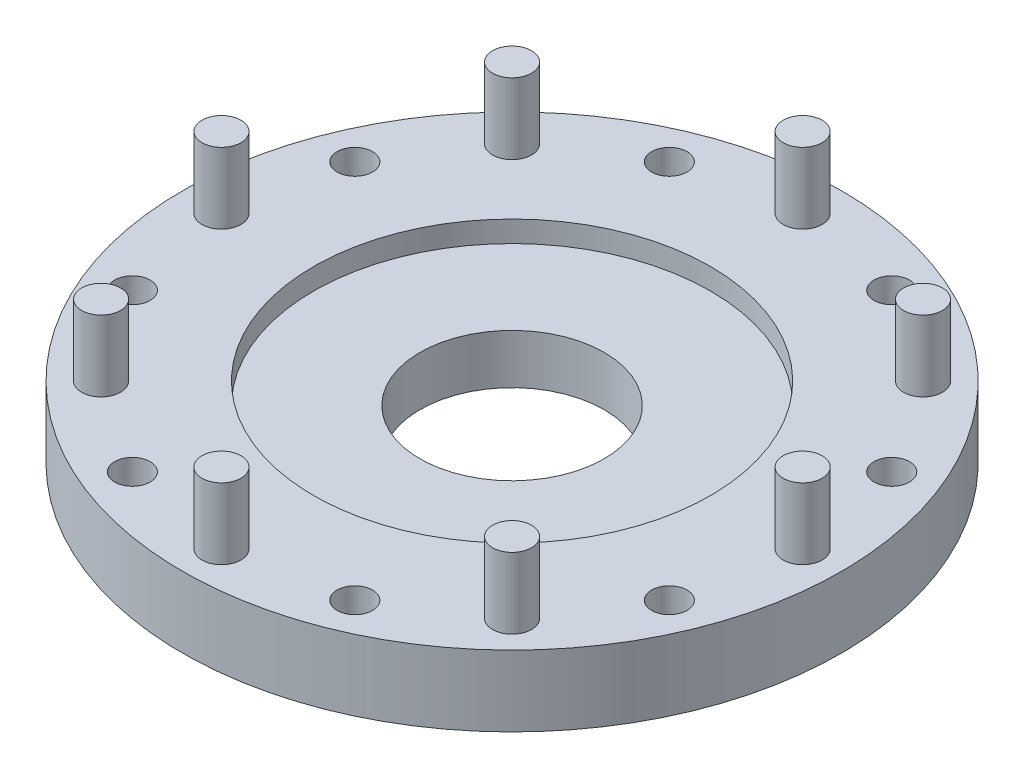
SolidWorks part; units mm, degrees
material "ABS"
ref_plane "Front Plane" through (0, 0, 0) normal (0, 0, 1) x (1, 0, 0)
ref_plane "Top Plane" through (0, 0, 0) normal (0, 1, 0) x (1, 0, 0)
ref_plane "Right Plane" through (0, 0, 0) normal (1, 0, 0) x (0, 0, -1)
sketch "Sketch1" plane through (0, 0, 0) normal (0, 0, 1) x (1, 0, 0)
  line L0 (0, -1.7519) -> (0, 48.3018) construction
  line L1 (-28, 10) -> (-46.5, 10)
  line L4 (-46.5, 10) -> (-46.5, 0)
  line L5 (-46.5, 0) -> (-13, 0)
  line L6 (-13, 0) -> (-13, 7)
  line L7 (-13, 7) -> (-28, 7)
  line L8 (-28, 7) -> (-28, 10)
  point P5 (0, 0)
  point P6 (0, 0)
  point P11 (0, 0)
  point P12 (-10.5, 31.1539)
  point P13 (-28, 36.7952)
  point P14 (0, 0)
  dimension "D1" = 46.5
  dimension "D3" = 3
  dimension "D2" = 28
  dimension "D4" = 13
  dimension "D5" = 10
revolve "Revolve1" add sketch "Sketch1" angle 360 about L0
sketch "Sketch2" plane through (0, 10, 0) normal (0, 1, 0) x (1, 0, 0)
  line L0 (0, 41) -> (0, 0) construction
  line L1 (0, 0) -> (15.69, 37.8791) construction
  circle A0 centre (0, 0) radius 41 construction
  circle A1 centre (0, 41) radius 2.75
  circle A2 centre (15.69, 37.8791) radius 2.5
  circle A3 centre (28.9914, 28.9914) radius 2.75
  circle A4 centre (37.8791, 15.69) radius 2.5
  circle A5 centre (41, 0) radius 2.75
  circle A6 centre (37.8791, -15.69) radius 2.5
  circle A7 centre (28.9914, -28.9914) radius 2.75
  circle A8 centre (15.69, -37.8791) radius 2.5
  circle A9 centre (0, -41) radius 2.75
  circle A10 centre (-15.69, -37.8791) radius 2.5
  circle A11 centre (-28.9914, -28.9914) radius 2.75
  circle A12 centre (-37.8791, -15.69) radius 2.5
  circle A13 centre (-41, 0) radius 2.75
  circle A14 centre (-37.8791, 15.69) radius 2.5
  circle A15 centre (-28.9914, 28.9914) radius 2.75
  circle A16 centre (-15.69, 37.8791) radius 2.5
  point P8 (0, 0)
  point P9 (0, 0)
  point P37 (0, 0)
  dimension "D1" = 82
  dimension "D2" = 5.5
  dimension "D3" = 5
  dimension "D4" = 22.5
  dimension "D5" = 8
extrude "Cut-Extrude1" cut sketch "Sketch2" against normal through all both and the other way through all
sketch "Sketch3" plane through (0, 0, 0) normal (0, 0, 1) x (1, 0, 0)
  line L0 (27.5, 4) -> (27.5, 0)
  line L2 (27.5, 0) -> (22.5, 0)
  line L3 (22.5, 0) -> (22.5, 4)
  line L6 (25, 4) -> (25, 0) construction
  line L7 (0, -19.0654) -> (0, 22.7714) construction
  line L8 (-46.5, 0) -> (46.5, 0) construction
  line L9 (27.5, 4) -> (22.5, 4)
  point P2 (25, 3.3621)
  dimension "D1" = 25
  dimension "D2" = 4
  dimension "D3" = 5
revolve "Cut-Revolve1" cut sketch "Sketch3" angle 360 about L7
sketch "Sketch4" plane through (0, 0, 0) normal (0, -1, 0) x (1, 0, 0)
  line L0 (-19.1541, 39.8791) -> (-19.1541, 35.8791)
  line L1 (-19.1541, 35.8791) -> (-15.69, 33.8791)
  line L2 (-15.69, 33.8791) -> (-12.2259, 35.8791)
  line L3 (-12.2259, 35.8791) -> (-12.2259, 39.8791)
  line L4 (-12.2259, 39.8791) -> (-15.69, 41.8791)
  line L5 (-15.69, 41.8791) -> (-19.1541, 39.8791)
  line L6 (-15.69, 41.8791) -> (-15.69, 33.8791) construction
  line L7 (18.5184, 40.7075) -> (14.6547, 41.7428)
  line L8 (14.6547, 41.7428) -> (11.8263, 38.9143)
  line L9 (11.8263, 38.9143) -> (12.8616, 35.0506)
  line L10 (12.8616, 35.0506) -> (16.7253, 34.0154)
  line L11 (16.7253, 34.0154) -> (19.5537, 36.8438)
  line L12 (19.5537, 36.8438) -> (18.5184, 40.7075)
  line L13 (41.8791, 15.69) -> (39.8791, 19.1541)
  line L14 (39.8791, 19.1541) -> (35.8791, 19.1541)
  line L15 (35.8791, 19.1541) -> (33.8791, 15.69)
  line L16 (33.8791, 15.69) -> (35.8791, 12.2259)
  line L17 (35.8791, 12.2259) -> (39.8791, 12.2259)
  line L18 (39.8791, 12.2259) -> (41.8791, 15.69)
  line L19 (40.7075, -18.5184) -> (41.7428, -14.6547)
  line L20 (41.7428, -14.6547) -> (38.9143, -11.8263)
  line L21 (38.9143, -11.8263) -> (35.0506, -12.8616)
  line L22 (35.0506, -12.8616) -> (34.0154, -16.7253)
  line L23 (34.0154, -16.7253) -> (36.8438, -19.5537)
  line L24 (36.8438, -19.5537) -> (40.7075, -18.5184)
  line L25 (15.69, -41.8791) -> (19.1541, -39.8791)
  line L26 (19.1541, -39.8791) -> (19.1541, -35.8791)
  line L27 (19.1541, -35.8791) -> (15.69, -33.8791)
  line L28 (15.69, -33.8791) -> (12.2259, -35.8791)
  line L29 (12.2259, -35.8791) -> (12.2259, -39.8791)
  line L30 (12.2259, -39.8791) -> (15.69, -41.8791)
  line L31 (-18.5184, -40.7075) -> (-14.6547, -41.7428)
  line L32 (-14.6547, -41.7428) -> (-11.8263, -38.9143)
  line L33 (-11.8263, -38.9143) -> (-12.8616, -35.0506)
  line L34 (-12.8616, -35.0506) -> (-16.7253, -34.0154)
  line L35 (-16.7253, -34.0154) -> (-19.5537, -36.8438)
  line L36 (-19.5537, -36.8438) -> (-18.5184, -40.7075)
  line L37 (-41.8791, -15.69) -> (-39.8791, -19.1541)
  line L38 (-39.8791, -19.1541) -> (-35.8791, -19.1541)
  line L39 (-35.8791, -19.1541) -> (-33.8791, -15.69)
  line L40 (-33.8791, -15.69) -> (-35.8791, -12.2259)
  line L41 (-35.8791, -12.2259) -> (-39.8791, -12.2259)
  line L42 (-39.8791, -12.2259) -> (-41.8791, -15.69)
  line L43 (-40.7075, 18.5184) -> (-41.7428, 14.6547)
  line L44 (-41.7428, 14.6547) -> (-38.9143, 11.8263)
  line L45 (-38.9143, 11.8263) -> (-35.0506, 12.8616)
  line L46 (-35.0506, 12.8616) -> (-34.0154, 16.7253)
  line L47 (-34.0154, 16.7253) -> (-36.8438, 19.5537)
  line L48 (-36.8438, 19.5537) -> (-40.7075, 18.5184)
  line L49 (11.8263, 38.9143) -> (19.5537, 36.8438) construction
  circle A0 centre (15.69, 37.8791) radius 2.5 construction
  circle A1 centre (0, 41) radius 2.75 construction
  circle A2 centre (0, 41) radius 2.75 construction
  circle A3 centre (15.69, 37.8791) radius 2.5 construction
  circle A4 centre (-15.69, 37.8791) radius 2.5 construction
  circle A5 centre (-15.69, 37.8791) radius 2.5 construction
  point P57 (0, 0)
  point P58 (0, 0)
  dimension "D1" = 120
  dimension "D2" = 120
  dimension "D3" = 8
  dimension "D4" = 8
extrude "Cut-Extrude2" cut sketch "Sketch4" against normal blind 5
sketch "Sketch5" plane through (0, 0, 0) normal (0, -1, 0) x (1, 0, 0)
  circle A0 centre (0, 41) radius 2.75 construction
  circle A1 centre (0, 41) radius 2.75
  circle A2 centre (28.9914, 28.9914) radius 2.75 construction
  circle A3 centre (41, 0) radius 2.75 construction
  circle A4 centre (28.9914, -28.9914) radius 2.75 construction
  circle A5 centre (0, -41) radius 2.75 construction
  circle A6 centre (-28.9914, -28.9914) radius 2.75 construction
  circle A7 centre (-41, 0) radius 2.75 construction
  circle A8 centre (-28.9914, 28.9914) radius 2.75 construction
  circle A9 centre (28.9914, 28.9914) radius 2.75
  circle A10 centre (41, 0) radius 2.75
  circle A11 centre (28.9914, -28.9914) radius 2.75
  circle A12 centre (0, -41) radius 2.75
  circle A13 centre (-28.9914, -28.9914) radius 2.75
  circle A14 centre (-41, 0) radius 2.75
  circle A15 centre (-28.9914, 28.9914) radius 2.75
extrude "Boss-Extrude1" add sketch "Sketch5" against normal blind 20
equation "\"Stator_OD\"= 60'No Tolerance given"
equation "\"A\"=35.81 'taken off spec sheet for 06808 (A)"
equation "\"Rotor_ID\"= 30'No Tolerance Given"
equation "\"back_bearing_Thickness\"= 5'-0.12"
equation "\"back_bearing_OD\"= 24'-0.009 https://www.mcmaster.com/5972K155/"
equation "\"Stator_Gap\"= 0.0375'+- 0.0125 (From 1.3.3.1 Kollmorgen manual)"
equation "\"Back_mount_hole\"= 1.75'To be tapped to M2 (USE LOCKTITE)"
equation "\"facePlate_Mount_Hole\"= 2.75'To be tapped to M3"
equation "\"final_shaftD\"= 12'To fit in harmonic"
equation "\"final_shaftL\"= 5.25+3+\"sheet_thick\"+\"connector_thick\"-3+\"harmon_coupleL\"+0.5-\"shaft_Ladjust\"'length to make everything nice and aligned"
equation "\"back_bearing_ID\"= 15'"
equation "\"back_bearing_IDOD\"= 16.5'measured off CAD, actually 16.75, but rounded down to nicer number"
equation "\"rotor_shaftD\"= \"Rotor_ID\" - (\"rotor-shaft_gap\")*2'"
equation "\"front_bearing_ID\"= 12'https://www.mcmaster.com/5972K154/"
equation "\"front_bearing_OD\"= 21'-0.009"
equation "\"front_bearing_IDOD\"= 13.5'Measured off CAD. Actually 13.75, but rounded down"
equation "\"rotor-shaft_gap\" = 0.0185 '+-0.0065 (from manual)"
equation "\"front_bearing_Thickness\"= 5'-0.12"
equation "\"rotor_thickness\"= 2.4'measured off CAD"
equation "\"rotor_height\"= 32.86'+-0.075 taken off spec sheet for 06826 (C)"
equation "\"B\"= 26.3'+-0.35 taken off spec sheet for 06826"
equation "\"key_L\"= 20'-0.2 https://www.mcmaster.com/2977N19/"
equation "\"key_H\"= 4'-0.03"
equation "\"key_W\"= 4'-0.03"
equation "\"harmon_keyH\"= 13.8'+0.1 from drawing"
equation "\"harmon_coupleL\"= 21.5' taken from drawing https://www.harmonicdrive.net/_hd/content/caddownloads/dxf/csg-2uh-lw_gearheads/csg-20-100-2uh-lw.pdf"
equation "\"harmon_diam\"= 93' from drawing"
equation "\"harmon_BCD\"= 82' from drawing"
equation "\"harmon_holeD1\"= 5.5' from drawing"
equation "\"harmon_holeD2\"= 5' from drawing"
equation "\"harmon_holeAng\"= 22.5' from drawing"
equation "\"sheet_thick\"= 1/8*25.4 'random, replace w actual sheet thickness when u feel like :)"
equation "\"D1@Sketch1\"=\"harmon_diam\"/2"
equation "\"D1@Sketch2\"=\"harmon_BCD\""
equation "\"D2@Sketch2\"=\"harmon_holeD1\""
equation "\"D3@Sketch2\"=\"harmon_holeD2\""
equation "\"D4@Sketch2\"=\"harmon_holeAng\""
equation "\"nut-thickness\"= 5 'idk measure the ones in the shop and adjust"
equation "\"D1@Cut-Extrude2\"=\"nut-thickness\""
equation "\"connector_thick\"= 10' random for now"
equation "\"D5@Sketch1\"=\"connector_thick\""
equation "\"shaft_Ladjust\"= 6.5' sorry. It's silly, but it works."
equation "\"D1@Boss-Extrude1\"=\"connector_thick\"+10"
